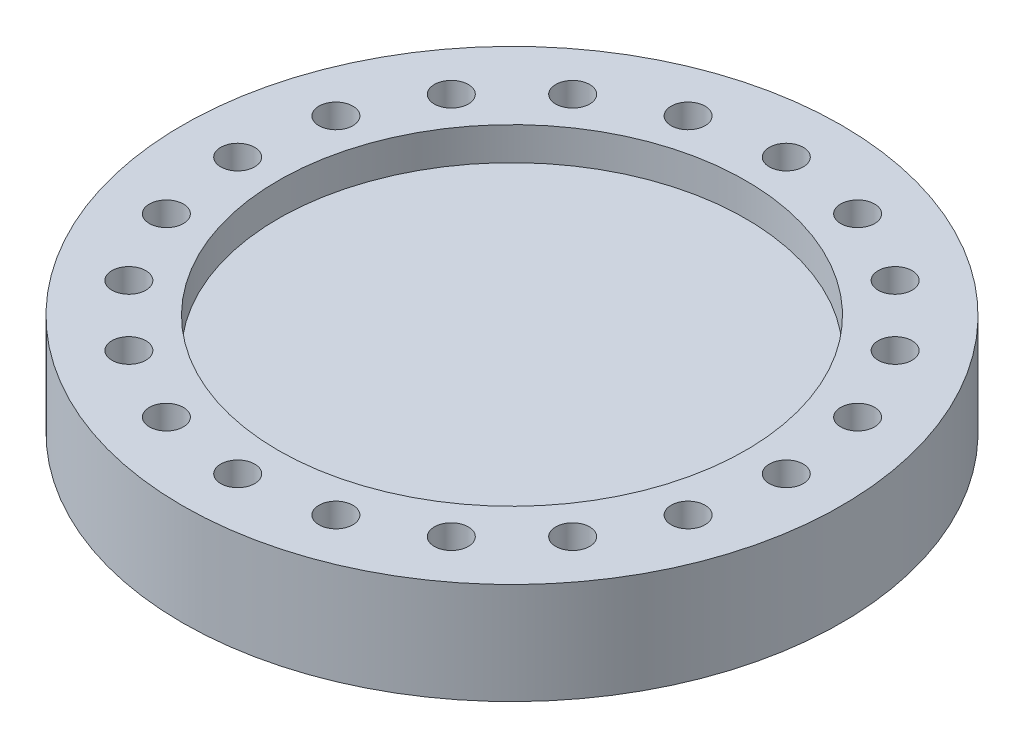
SolidWorks part; units mm, degrees
ref_plane "Front Plane" through (0, 0, 0) normal (0, 0, 1) x (1, 0, 0)
ref_plane "Top Plane" through (0, 0, 0) normal (0, 1, 0) x (1, 0, 0)
ref_plane "Right Plane" through (0, 0, 0) normal (1, 0, 0) x (0, 0, -1)
sketch "Sketch1" plane through (0, 0, 0) normal (0, 1, 0) x (1, 0, 0)
  line L0 (15.8996, 21.8839) -> (0, 0) construction
  line L1 (0, 0) -> (27.05, 0) construction
  circle A0 centre (0, 0) radius 27.05 construction
  circle A1 centre (15.8996, 21.8839) radius 1.675
  circle A2 centre (0, 0) radius 32.5
  circle A3 centre (21.8839, 15.8996) radius 1.675
  circle A4 centre (25.7261, 8.3589) radius 1.675
  circle A5 centre (27.05, 0) radius 1.675
  circle A6 centre (25.7261, -8.3589) radius 1.675
  circle A7 centre (21.8839, -15.8996) radius 1.675
  circle A8 centre (15.8996, -21.8839) radius 1.675
  circle A9 centre (8.3589, -25.7261) radius 1.675
  circle A10 centre (0, -27.05) radius 1.675
  circle A11 centre (-8.3589, -25.7261) radius 1.675
  circle A12 centre (-15.8996, -21.8839) radius 1.675
  circle A13 centre (-21.8839, -15.8996) radius 1.675
  circle A14 centre (-25.7261, -8.3589) radius 1.675
  circle A15 centre (-27.05, 0) radius 1.675
  circle A16 centre (-25.7261, 8.3589) radius 1.675
  circle A17 centre (-21.8839, 15.8996) radius 1.675
  circle A18 centre (-15.8996, 21.8839) radius 1.675
  circle A19 centre (-8.3589, 25.7261) radius 1.675
  circle A20 centre (0, 27.05) radius 1.675
  circle A21 centre (8.3589, 25.7261) radius 1.675
  point P8 (23.5359, 12.8553)
  point P11 (0, 0)
  point P49 (0, 0)
  dimension "D2" = 3.35
  dimension "D3" = 54.1
  dimension "D4" = 65
  dimension "D1" = 54
  dimension "D5" = 20
extrude "Boss-Extrude1" add sketch "Sketch1" along normal blind 10
sketch "Sketch2" plane through (0, 10, 0) normal (0, 1, 0) x (1, 0, 0)
  circle A0 centre (0, 0) radius 23.05
  dimension "D1" = 46.1
extrude "Cut-Extrude1" cut sketch "Sketch2" against normal blind 3.25
